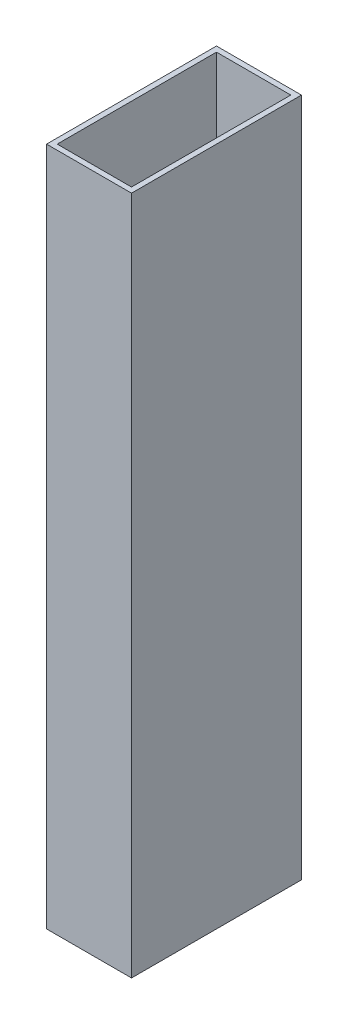
SolidWorks part; units mm, degrees
material "6061-T6 (SS)"
ref_plane "Front" through (0, 0, 0) normal (0, 0, 1) x (1, 0, 0)
ref_plane "Top" through (0, 0, 0) normal (0, 1, 0) x (1, 0, 0)
ref_plane "Right" through (0, 0, 0) normal (1, 0, 0) x (0, 0, -1)
sketch "Sketch1" plane through (0, 0, 0) normal (0, 1, 0) x (1, 0, 0)
  line L1 (12.7, 25.4) -> (-12.7, 25.4)
  line L2 (12.7, 25.4) -> (12.7, -25.4)
  line L3 (12.7, -25.4) -> (-12.7, -25.4)
  line L4 (-12.7, 25.4) -> (-12.7, -25.4)
  line L5 (12.7, 25.4) -> (-12.7, -25.4) construction
  line L6 (12.7, -25.4) -> (-12.7, 25.4) construction
  point P0 (0, 0)
  dimension "D1" = 25.4
  dimension "D2" = 50.8
extrude "Extrude-Thin1" add sketch "Sketch1" along normal blind 203.2 thin thin type one direction reverse wall 1.5875
